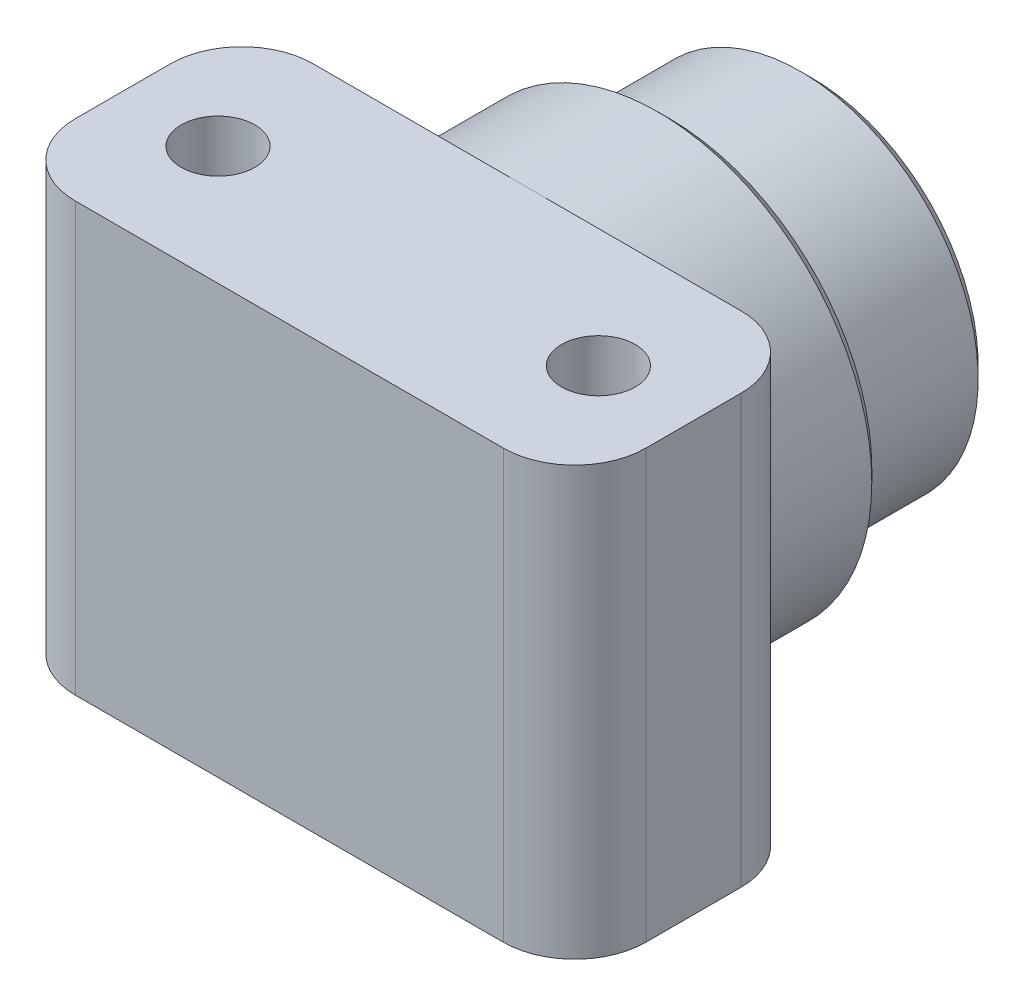
SolidWorks part; units mm, degrees
material "6061 Alloy"
ref_plane "前视基准面" through (0, 0, 0) normal (0, 0, 1) x (1, 0, 0)
ref_plane "上视基准面" through (0, 0, 0) normal (0, 1, 0) x (1, 0, 0)
ref_plane "右视基准面" through (0, 0, 0) normal (1, 0, 0) x (0, 0, -1)
sketch "草图1" plane through (0, 0, 0) normal (0, 0, 1) x (1, 0, 0)
  line L1 (-12, 9) -> (12, 9)
  line L2 (-12, 9) -> (-12, -9)
  line L3 (-12, -9) -> (12, -9)
  line L4 (12, 9) -> (12, -9)
  line L5 (-12, 9) -> (12, -9) construction
  line L6 (-12, -9) -> (12, 9) construction
  point P0 (0, 0)
  dimension "D1" = 24
  dimension "D2" = 18
extrude "凸台-拉伸1" add sketch "草图1" along normal blind 10
sketch "草图2" plane through (0, 0, 0) normal (0, 0, 1) x (1, 0, 0)
  circle A1 centre (0, 0) radius 9
  dimension "D2" = 18
extrude "凸台-拉伸2" add sketch "草图2" against normal blind 6
sketch "草图4" plane through (0, 9, 0) normal (0, 1, 0) x (1, 0, 0)
  line L0 (-12, -5) -> (12, -5) construction
  line L1 (-12, -10) -> (-12, 0) construction
  line L2 (12, -10) -> (12, 0) construction
  circle A0 centre (-8, -5) radius 1.55
  circle A1 centre (8, -5) radius 1.55
  dimension "D1" = 3.1
  dimension "D2" = 3.1
  dimension "D4" = 4
  dimension "D3" = 4
extrude "切除-拉伸2" cut sketch "草图4" against normal blind 37.0135
ref_plane "基准面1" through (9, 0, 0) normal (1, 0, 0) x (0, 0, -1)
sketch "Sketch1" plane through (0, 0, -6) normal (0, 0, -1) x (-1, 0, 0)
  circle A0 centre (0, 0) radius 7.475
  dimension "D1" = 14.95
extrude "Boss-Extrude1" add sketch "Sketch1" along normal blind 6
chamfer "Chamfer1" distance 0.5 angle 45 2 edges at (9, 0, -6) (-7.475, 0, -12)
fillet "Fillet1" radius 3 4 edges at (12, 0, 10) (12, 0, 0) (-12, 0, 10) (-12, 0, 0)
